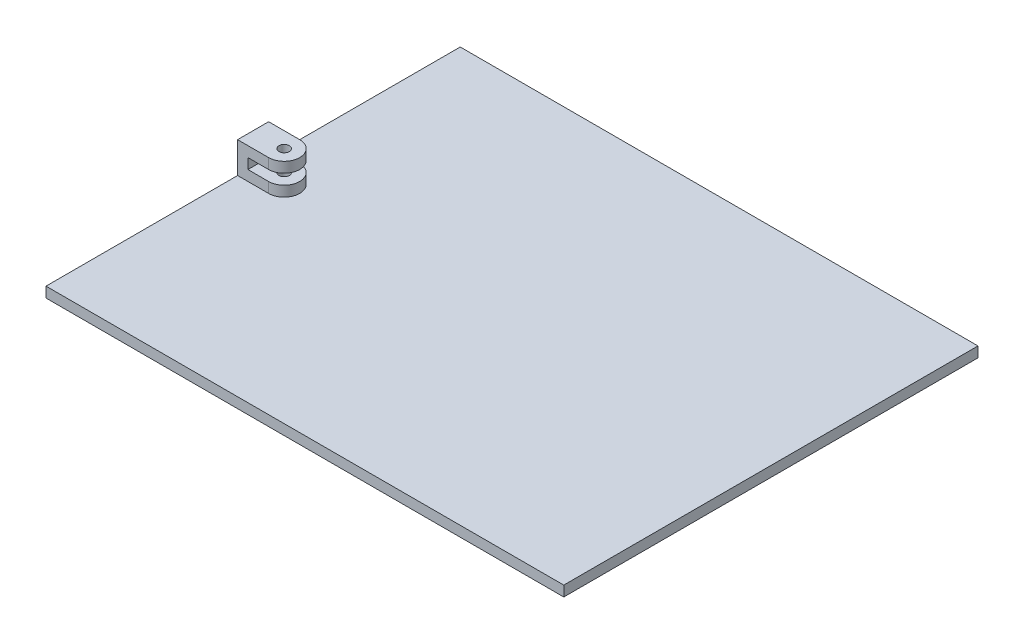
SolidWorks part; units mm, degrees
ref_plane "Ön Düzlem" through (0, 0, 0) normal (0, 0, 1) x (1, 0, 0)
ref_plane "Üst Düzlem" through (0, 0, 0) normal (0, 1, 0) x (1, 0, 0)
ref_plane "Sağ Düzlem" through (0, 0, 0) normal (1, 0, 0) x (0, 0, -1)
sketch "Sketch1" plane through (0, 0, 0) normal (0, 1, 0) x (1, 0, 0)
  line L0 (0, 15) -> (-20, 15)
  line L1 (-20, 15) -> (-20, -15)
  line L2 (-20, -15) -> (0, -15)
  circle A0 centre (0, 0) radius 5
  arc A1 (0, -15) -> (0, 15) centre (0, 0) ccw
  dimension "D1" = 10
  dimension "D2" = 15
  dimension "D3" = 20
extrude "Boss-Extrude1" add sketch "Sketch1" against normal blind 10
sketch "Sketch2" plane through (-20, 0, 0) normal (-1, 0, 0) x (0, 0, 1)
  line L0 (-15, -10) -> (15, -10) construction
  line L1 (15, 0) -> (-15, 0)
  line L2 (15, 0) -> (15, -30)
  line L3 (15, -30) -> (-15, -30)
  line L4 (-15, 0) -> (-15, -30)
  dimension "D1" = 20
  dimension "D2" = 30
extrude "Boss-Extrude2" add sketch "Sketch2" along normal blind 10
extrude "Boss-Extrude3" add sketch "Sketch1<2>" along normal blind 10 from offset 30 offset against normal yes
sketch "Sketch1<2>" plane through (0, 0, 0) normal (0, 1, 0) x (1, 0, 0) same geometry as "Sketch1"
sketch "Sketch3" plane through (0, -30, 0) normal (0, -1, 0) x (1, 0, 0)
  line L1 (-30, -200) -> (470, -200)
  line L2 (-30, -200) -> (-30, 200)
  line L3 (-30, 200) -> (470, 200)
  line L4 (470, -200) -> (470, 200)
  dimension "D1" = 400
  dimension "D2" = 200
  dimension "D3" = 500
  dimension "D4" = 30
extrude "Boss-Extrude4" add sketch "Sketch3" along normal blind 10
sketch "Sketch6" plane through (0, -30, 0) normal (0, 1, 0) x (1, 0, 0)
  circle A0 centre (250, 0) radius 50
  point P6 (300, 0)
  dimension "D1" = 250
  dimension "D2" = 0
